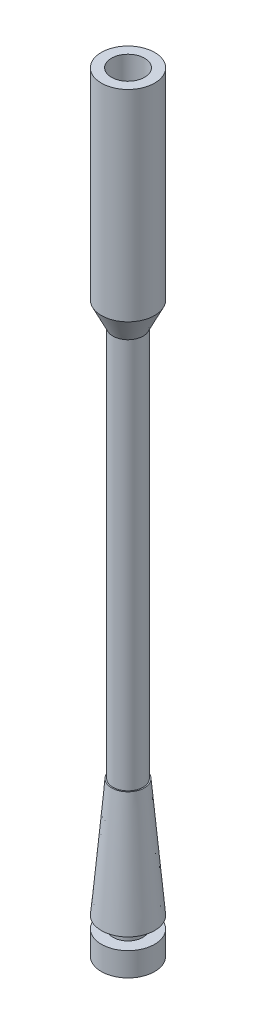
SolidWorks part; units mm, degrees
ref_plane "Front Plane" through (0, 0, 0) normal (0, 0, 1) x (1, 0, 0)
ref_plane "Top Plane" through (0, 0, 0) normal (0, 1, 0) x (1, 0, 0)
ref_plane "Right Plane" through (0, 0, 0) normal (1, 0, 0) x (0, 0, -1)
sketch "Sketch1" plane through (0, 0, 0) normal (0, 1, 0) x (1, 0, 0)
  circle A0 centre (-0.522, 0.5111) radius 1.375
  circle A1 centre (-0.522, 0.5111) radius 2.25
  dimension "D1" = 2.75
  dimension "D2" = 4.5
extrude "Boss-Extrude1" add sketch "Sketch1" along normal blind 10 draft 5 contours A1
extrude "Boss-Extrude2" add sketch "Sketch1<3>" along normal blind 1 contours A0 region at (-0.522, 0, -0.5111)
sketch "Sketch1<3>" plane through (0, 0, 0) normal (0, 1, 0) x (1, 0, 0) same geometry as "Sketch1"
sketch "Sketch5" plane through (0, 0, 0) normal (0, -1, 0) x (1, 0, 0)
  circle A3 centre (-0.522, -0.5111) radius 1.25
  dimension "D1" = 2.5
extrude "Boss-Extrude3" add sketch "Sketch5" along normal blind 1 contours A3
sketch "Sketch6" plane through (0, -1, 0) normal (0, -1, 0) x (1, 0, 0)
  circle A0 centre (-0.522, -0.5111) radius 2.25
  dimension "D1" = 4.5
extrude "Boss-Extrude4" add sketch "Sketch6" along normal blind 2
sketch "Sketch14" plane through (0, 10, 0) normal (0, 1, 0) x (1, 0, 0)
  circle A0 centre (-0.522, 0.5111) radius 1.2745
extrude "Boss-Extrude6" add sketch "Sketch14" along normal blind 33
sketch "Sketch15" plane through (0, 43, 0) normal (0, 1, 0) x (1, 0, 0)
  circle A1 centre (-0.522, 0.5111) radius 1.2745
extrude "Boss-Extrude8" add sketch "Sketch15" along normal blind 2 draft 26 draft outward yes
sketch "Sketch17" plane through (0, 45, 0) normal (0, 1, 0) x (1, 0, 0)
  circle A0 centre (-0.522, 0.5111) radius 2.25
  dimension "D1" = 4.5
extrude "Boss-Extrude9" add sketch "Sketch17" along normal blind 17
sketch "Sketch18" plane through (0, 62, 0) normal (0, 1, 0) x (1, 0, 0)
  circle A0 centre (-0.522, 0.5111) radius 1.4
  dimension "D1" = 2.8
extrude "Cut-Extrude2" cut sketch "Sketch18" against normal blind 15
